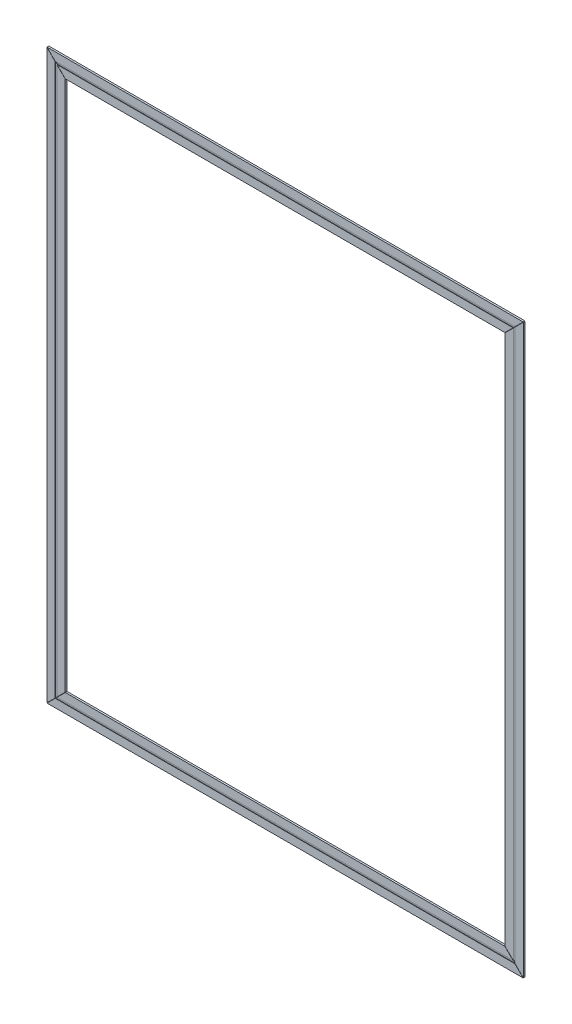
SolidWorks part; units mm, degrees
ref_plane "Front Plane" through (0, 0, 0) normal (0, 0, 1) x (1, 0, 0)
ref_plane "Top Plane" through (0, 0, 0) normal (0, 1, 0) x (1, 0, 0)
ref_plane "Right Plane" through (0, 0, 0) normal (1, 0, 0) x (0, 0, -1)
sketch "Croquis1" plane through (0, 0, 0) normal (0, 0, 1) x (1, 0, 0)
  line L0 (-240, -290) -> (-240, 290)
  line L1 (-240, -290) -> (240, -290)
  line L2 (-240, 290) -> (240, 290)
  line L3 (240, -290) -> (240, 290)
  line L4 (-240, -290) -> (240, 290) construction
  line L5 (-240, 290) -> (240, -290) construction
  line L6 (-260, -310) -> (-260, 310)
  line L7 (-260, -310) -> (260, -310)
  line L8 (-260, 310) -> (260, 310)
  line L9 (260, -310) -> (260, 310)
  line L10 (-260, -310) -> (260, 310) construction
  line L11 (-260, 310) -> (260, -310) construction
  line L12 (-260, -310) -> (-240, -290)
  line L13 (240, -290) -> (260, -310)
  line L14 (240, 290) -> (260, 310)
  line L15 (-240, 290) -> (-260, 310)
  line L16 (-250, -300) -> (-250, 300)
  line L17 (-250, 300) -> (250, 300)
  line L18 (250, 300) -> (250, -300)
  line L19 (250, -300) -> (-250, -300)
  line L20 (249, 299) -> (249, -299)
  line L21 (249, 299) -> (-249, 299)
  line L22 (249, -299) -> (-249, -299)
  line L23 (-249, 299) -> (-249, -299)
  line L24 (249, 299) -> (-249, -299) construction
  line L25 (249, -299) -> (-249, 299) construction
  line L26 (251, 301) -> (251, -301)
  line L27 (251, 301) -> (-251, 301)
  line L28 (251, -301) -> (-251, -301)
  line L29 (-251, 301) -> (-251, -301)
  line L30 (251, 301) -> (-251, -301) construction
  line L31 (251, -301) -> (-251, 301) construction
  point P1 (0, 0)
  point P2 (0, 0)
  point P16 (0, 0)
  point P17 (0, 0)
  dimension "D1" = 20
  dimension "D2" = 20
  dimension "D3" = 480
  dimension "D4" = 580
  dimension "D5" = 1
  dimension "D6" = 1
  dimension "D7" = 1
  dimension "D8" = 1
extrude "Saliente-Extruir1" add sketch "Croquis1" along normal blind 2 contours L15 L23 L12 L0 | L29 L15 L6 L12 | L27 L14 L8 L15 | L14 L21 L15 L2 | L20 L14 L3 L13 | L14 L26 L13 L9 | L13 L28 L12 L7 | L22 L13 L1 L12 region at (-244.5229, 0, 0) region at (0, -294.5276, 0) region at (0, 294.5276, 0) region at (244.5229, 0, 0) region at (0, -305.5264, 0) region at (-255.5221, 0, 0) region at (0, 305.5264, 0) region at (255.5221, 0, 0)
extrude "Saliente-Extruir2" add sketch "Croquis1<3>" along normal blind 1.5 contours L23 L15 L16 L12 | L15 L29 L12 L16 | L21 L14 L17 L15 | L14 L27 L15 L17 | L13 L22 L12 L19 | L28 L13 L19 L12 | L14 L20 L13 L18 | L26 L14 L18 L13 region at (0, -299.5003, 0) region at (-249.5003, 0, 0) region at (0, 299.5003, 0) region at (249.5003, 0, 0) region at (0, -300.5003, 0) region at (-250.5003, 0, 0) region at (0, 300.5003, 0) region at (250.5003, 0, 0)
sketch "Croquis1<3>" plane through (0, 0, 0) normal (0, 0, 1) x (1, 0, 0) same geometry as "Croquis1"
sketch "Croquis2" plane through (0, 0, 2) normal (0, 0, 1) x (1, 0, 0)
  line L0 (-240, 289.8) -> (-260, 309.8)
  line L1 (-240, -290) -> (-240, 290) construction
  line L2 (-260, -310) -> (-260, 310) construction
  line L3 (-260, 309.8) -> (-260, 310)
  line L4 (-260, 310) -> (260, 310) construction
  line L5 (-260, 310) -> (-259.8, 310)
  line L6 (-259.8, 310) -> (-239.8, 290)
  line L7 (-240, 290) -> (240, 290) construction
  line L8 (-239.8, 290) -> (-240, 290)
  line L9 (-240, 290) -> (-240, 289.8)
  line L10 (0, 0) -> (0, 168.7335) construction
  line L11 (0, 0) -> (-128.9124, 0) construction
  line L12 (240, 290) -> (240, 289.8)
  line L13 (239.8, 290) -> (240, 290)
  line L14 (259.8, 310) -> (239.8, 290)
  line L15 (260, 310) -> (259.8, 310)
  line L16 (260, 309.8) -> (260, 310)
  line L17 (240, 289.8) -> (260, 309.8)
  line L18 (240, -289.8) -> (260, -309.8)
  line L19 (260, -309.8) -> (260, -310)
  line L20 (260, -310) -> (259.8, -310)
  line L21 (259.8, -310) -> (239.8, -290)
  line L22 (239.8, -290) -> (240, -290)
  line L23 (240, -290) -> (240, -289.8)
  line L24 (-240, -290) -> (-240, -289.8)
  line L25 (-239.8, -290) -> (-240, -290)
  line L26 (-259.8, -310) -> (-239.8, -290)
  line L27 (-260, -310) -> (-259.8, -310)
  line L28 (-260, -309.8) -> (-260, -310)
  line L29 (-240, -289.8) -> (-260, -309.8)
  dimension "D1" = 0.2
  dimension "D2" = 0.2
  dimension "D3" = 0.2
  dimension "D4" = 0.2
extrude "Cortar-Extruir1" cut sketch "Croquis2" against normal blind 21
